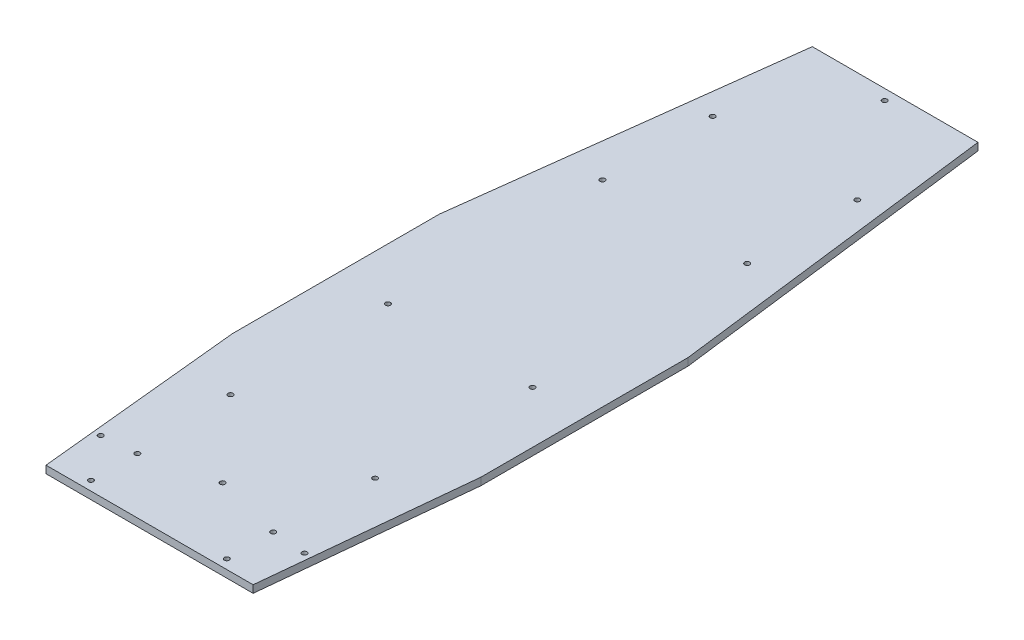
SolidWorks part; units mm, degrees
material "Pine"
ref_plane "Front Plane" through (0, 0, 0) normal (0, 0, 1) x (1, 0, 0)
ref_plane "Top Plane" through (0, 0, 0) normal (0, 1, 0) x (1, 0, 0)
ref_plane "Right Plane" through (0, 0, 0) normal (1, 0, 0) x (0, 0, -1)
sketch "Sketch1" plane through (0, 0, 0) normal (0, 1, 0) x (1, 0, 0)
  line L2 (-150, -125) -> (-150, 125)
  line L4 (150, -125) -> (150, 125)
  line L5 (-100, 525) -> (-150, 125)
  line L6 (-150, -125) -> (-125, -375)
  line L7 (-125, -375) -> (125, -375)
  line L16 (125, -375) -> (150, -125)
  line L17 (150, 125) -> (100, 525)
  line L18 (-100, 525) -> (100, 525)
  point P0 (0, 0)
  point P6 (0, 0)
  dimension "D1" = 300
  dimension "D2" = 250
  dimension "D3" = 125
  dimension "D4" = 200
  dimension "D5" = 125
  dimension "D6" = 100
  dimension "D7" = 900
  dimension "D8" = 400
extrude "Boss-Extrude1" add sketch "Sketch1" along normal blind 9
sketch "Sketch3" plane through (0, 9, 0) normal (0, 1, 0) x (1, 0, 0)
  line L0 (-125, -375) -> (125, -375) construction
  line L1 (-100, 525) -> (100, 525)
  line L2 (-100, 525) -> (-100, -375)
  line L3 (-100, -375) -> (100, -375)
  line L4 (100, 525) -> (100, -375)
  line L6 (0, 525) -> (0, -375) construction
  line L7 (-100, -375) -> (100, -375)
  line L8 (-100, -375) -> (-100, -299.5)
  line L9 (-100, -299.5) -> (100, -299.5)
  line L10 (100, -375) -> (100, -299.5)
  point P7 (0, 512.3)
  point P8 (-87.3, 392)
  point P9 (-87.3, 259)
  point P10 (-87.3, 0)
  point P11 (0, -286.8)
  point P14 (-87.3, -190)
  point P19 (87.3, -190)
  point P20 (87.3, 0)
  point P21 (87.3, 259)
  point P22 (87.3, 392)
  point P23 (0, 525)
  dimension "D1" = 200
  dimension "D2" = 12.7
  dimension "D3" = 12.7
  dimension "D4" = 133
  dimension "D5" = 133
  dimension "D6" = 125
  dimension "D7" = 65
  dimension "D8" = 75.5
  dimension "D9" = 12.7
hole_wizard "Ø6.0 (6) Diameter Hole1" positions "3DSketch3" profile "Sketch5" hole size "Ø6.0" standard "ANSI Metric" end condition through all
sketch3d "3DSketch3"
  point P0 (0, 9, -512.3)
  point P3 (-87.3, 9, -392)
  point P6 (-87.3, 9, -259)
  point P9 (87.3, 9, -259)
  point P12 (87.3, 9, -392)
  point P15 (87.3, 9, 0)
  point P18 (-87.3, 9, 0)
  point P21 (-87.3, 9, 190)
  point P24 (87.3, 9, 190)
  point P28 (0, 9, 286.8)
sketch "Sketch5" plane through (0, 9, -512.3) normal (1, 0, 0) x (0, 0, 1)
  line L0 (0, 0) -> (0, 9)
  line L1 (0, 9) -> (6, 9)
  line L2 (3, 6) -> (3, 0)
  line L5 (3, 0) -> (0, 0)
  line L7 (6, 9) -> (3, 6)
  line L8 (-6, 9) -> (-3, 6) construction
  line L11 (0, -6.35) -> (0, 107.95) construction
  dimension "Thru Hole Dia." = 6
  dimension "Thru Hole Depth" = 9
  dimension "Far C'Sink Dia." = 12
  dimension "Far C'Sink Angle" = 90
hole_wizard "Ø6.0 (6) Diameter Hole3" positions "3DSketch5" profile "Sketch7" hole size "Ø6.0" standard "ANSI Metric"
sketch3d "3DSketch5"
  line L0 (0, 3, -512.3) -> (0, 9, -512.3) construction
  line L1 (87.3, 3, -392) -> (87.3, 9, -392) construction
  line L2 (-87.3, 3, -392) -> (-87.3, 9, -392) construction
  line L3 (-87.3, 3, -259) -> (-87.3, 9, -259) construction
  line L4 (87.3, 3, -259) -> (87.3, 9, -259) construction
  line L5 (87.3, 3, 0) -> (87.3, 9, 0) construction
  line L6 (-87.3, 3, 0) -> (-87.3, 9, 0) construction
  line L7 (-87.3, 3, 190) -> (-87.3, 9, 190) construction
  line L8 (87.3, 3, 190) -> (87.3, 9, 190) construction
  line L9 (0, 3, 286.8) -> (0, 9, 286.8) construction
  point P0 (0, 0, -512.3)
  point P4 (87.3, 0, -392)
  point P8 (-87.3, 0, -392)
  point P12 (-87.3, 0, -259)
  point P16 (87.3, 0, -259)
  point P20 (87.3, 0, 0)
  point P24 (-87.3, 0, 0)
  point P28 (-87.3, 0, 190)
  point P32 (87.3, 0, 190)
  point P36 (0, 0, 286.8)
sketch "Sketch7" plane through (0, 0, -512.3) normal (1, 0, 0) x (0, 0, -1)
  line L0 (0, 0) -> (0, 36.3026)
  line L1 (0, 36.3026) -> (3, 34.5)
  line L2 (3, 34.5) -> (3, 0)
  line L5 (3, 0) -> (0, 0)
  line L10 (0, 36.3026) -> (-3, 34.5) construction
  line L11 (0, -6.35) -> (0, 107.95) construction
  dimension "Hole Dia." = 6
  dimension "Hole Depth" = 34.5
  dimension "Drill Angle" = 118
hole_wizard "Ø6.0 (6) Diameter Hole4" positions "Sketch9" profile "Sketch10" hole size "Ø6.0" standard "ANSI Metric" end condition through all
sketch "Sketch9" plane through (0, 9, 0) normal (0, 1, 0) x (1, 0, 0)
  point P0 (123, -311)
  point P3 (-123, -311)
sketch "Sketch10" plane through (123, 9, 311) normal (1, 0, 0) x (0, 0, 1)
  line L0 (0, 0) -> (0, 9)
  line L1 (0, 9) -> (6, 9)
  line L2 (3, 6) -> (3, 0)
  line L5 (3, 0) -> (0, 0)
  line L7 (6, 9) -> (3, 6)
  line L8 (-6, 9) -> (-3, 6) construction
  line L11 (0, -6.35) -> (0, 107.95) construction
  dimension "Thru Hole Dia." = 6
  dimension "Thru Hole Depth" = 9
  dimension "Far C'Sink Dia." = 12
  dimension "Far C'Sink Angle" = 90
hole_wizard "Ø6.0 (6) Diameter Hole5" positions "Sketch11" profile "Sketch12" hole size "Ø6.0" standard "ANSI Metric" end condition through all
sketch "Sketch11" plane through (0, 9, 0) normal (0, 1, 0) x (1, 0, 0)
  point P0 (-82, -363.75)
  point P3 (-82, -307.75)
  point P6 (82, -363.75)
  point P9 (82, -307.75)
sketch "Sketch12" plane through (-82, 9, 363.75) normal (1, 0, 0) x (0, 0, 1)
  line L0 (0, 0) -> (0, 9)
  line L1 (0, 9) -> (6, 9)
  line L2 (3, 6) -> (3, 0)
  line L5 (3, 0) -> (0, 0)
  line L7 (6, 9) -> (3, 6)
  line L8 (-6, 9) -> (-3, 6) construction
  line L11 (0, -6.35) -> (0, 107.95) construction
  dimension "Thru Hole Dia." = 6
  dimension "Thru Hole Depth" = 9
  dimension "Far C'Sink Dia." = 12
  dimension "Far C'Sink Angle" = 90
